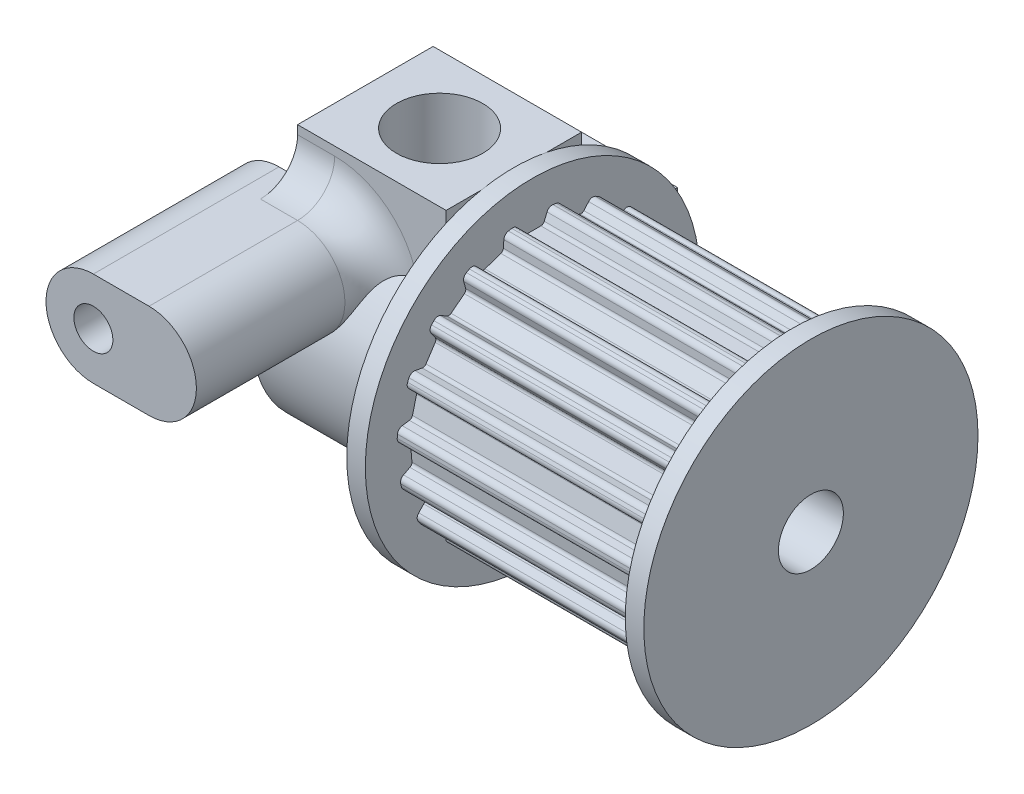
SolidWorks part; units mm, degrees
material "PLA Black"
ref_plane "Front" through (0, 0, 0) normal (0, 0, 1) x (1, 0, 0)
ref_plane "Top" through (0, 0, 0) normal (0, 1, 0) x (1, 0, 0)
ref_plane "Right" through (0, 0, 0) normal (1, 0, 0) x (0, 0, -1)
sketch "Sketch1" plane through (0, 0, 0) normal (1, 0, 0) x (0, 0, -1)
  line L0 (1.118, 1) -> (-1.118, 1) construction
  line L1 (-3.65, 4.8249) -> (3.65, 4.8249)
  line L2 (4.8249, 3.65) -> (4.8249, -3.65)
  line L3 (0, 0) -> (11.6334, 0) construction
  line L4 (0, 0) -> (0, 8.6732) construction
  arc A0 (-1.118, 1) -> (1.118, 1) centre (0, 0) ccw construction
  circle A1 centre (0, 0) radius 1.75
  arc A2 (4.8249, -3.65) -> (-3.65, 4.8249) centre (0, 0) cw
  arc A3 (4.8249, 3.65) -> (3.65, 4.8249) centre (0, 0) ccw
  dimension "D1" = 3
  dimension "D3" = 0.25
  dimension "D5" = 6.05
  dimension "D2" = 1
  dimension "D4" = 7.3
extrude "Boss-Extrude1" add sketch "Sketch1" along normal mid plane 8
sketch "Sketch2" plane through (0, 4.8249, 0) normal (0, 1, 0) x (1, 0, 0)
  circle A0 centre (0, 0) radius 2.325
  dimension "D1" = 4.65
extrude "Cut-Extrude1" cut sketch "Sketch2" against normal blind 5
sketch "Sketch7" plane through (4, 0, 0) normal (1, 0, 0) x (0, 0, -1)
  circle A0 centre (0, 0) radius 1.75 construction
  circle A1 centre (0, 0) radius 7.3
  circle A2 centre (0, 0) radius 1.75
  dimension "D1" = 14.6
extrude "Boss-Extrude5" add sketch "Sketch7" along normal blind 15
sketch "Sketch8" plane through (19, 0, 0) normal (1, 0, 0) x (0, 0, -1)
  line L0 (-0.4541, 6.5499) -> (0.4528, 6.5499)
  line L1 (0.6374, 6.6734) -> (0.7865, 7.0333)
  line L2 (-0.6389, 6.6734) -> (-0.788, 7.0333)
  line L6 (0, 9.2013) -> (0, 0) construction
  arc A0 (0.4528, 6.5499) -> (0.6374, 6.6734) centre (0.4526, 6.7499) ccw
  arc A1 (-0.4541, 6.5499) -> (-0.6389, 6.6734) centre (-0.4541, 6.7499) cw
  arc A2 (0.7865, 7.0333) -> (1.1093, 7.2152) centre (1.0638, 6.9187) cw
  arc A3 (-0.788, 7.0333) -> (-1.1108, 7.215) centre (-1.0652, 6.9185) ccw
  circle A4 centre (0, 0) radius 7.3 construction
  arc A5 (-1.1108, 7.215) -> (1.1093, 7.2152) centre (0, 0) cw
  point P3 (-0.0007, 6.5499)
  point P15 (0, 9.84)
extrude "Cut-Extrude3" cut sketch "Sketch8" against normal up to surface (15 mm away) up to face at (4, 0, -7.3)
pattern_circular "CirPattern1" count 19 over 360 about axis through (19, 0, 0) along (-1, 0, 0) of "Cut-Extrude3"
sketch "Sketch9" plane through (19, 0, 0) normal (1, 0, 0) x (0, 0, -1)
  circle A0 centre (0, 0) radius 9
  circle A1 centre (0, 0) radius 1.75 construction
  circle A2 centre (0, 0) radius 1.75
  dimension "D1" = 18
extrude "Boss-Extrude6" add sketch "Sketch9" along normal blind 1
sketch "Sketch10" plane through (4, 0, 0) normal (-1, 0, 0) x (0, 0, 1)
  circle A0 centre (0, 0) radius 9
  circle A1 centre (0, 0) radius 9 construction
  circle A2 centre (0, 0) radius 1.75 construction
  circle A3 centre (0, 0) radius 1.75
extrude "Boss-Extrude7" add sketch "Sketch10" against normal blind 1
sketch "Sketch3" plane through (0, 0, -4.8249) normal (0, 0, -1) x (-1, 0, 0)
  circle A0 centre (0, 0) radius 2.325
  dimension "D1" = 4.65
extrude "Cut-Extrude2" cut sketch "Sketch3" against normal blind 5
sketch "Sketch4" plane through (0, 4.8249, 0) normal (0, 1, 0) x (1, 0, 0)
  line L0 (4, 3.65) -> (-4, 3.65) construction
  line L2 (4, -3.65) -> (-4, -3.65) construction
  line L3 (-4, 3.65) -> (-4, -3.65) construction
  line L4 (4, 3.65) -> (-4, 3.65)
  line L5 (4, 3.65) -> (4, -3.65)
  line L6 (4, -3.65) -> (-4, -3.65)
  line L7 (-4, 3.65) -> (-4, -3.65)
  line L8 (4, 7.3) -> (4, -7.3) construction
  circle A0 centre (0, 0) radius 2.325 construction
  circle A1 centre (0, 0) radius 2.325
extrude "Boss-Extrude2" add sketch "Sketch4" along normal blind 4
sketch "Sketch5" plane through (0, 0, -4.8249) normal (0, 0, -1) x (-1, 0, 0)
  line L0 (-4, 3.65) -> (4, 3.65) construction
  line L1 (4, -3.65) -> (4, 3.65) construction
  line L2 (-4, -3.65) -> (4, -3.65) construction
  line L4 (-4, 3.65) -> (4, 3.65)
  line L5 (4, -3.65) -> (4, 3.65)
  line L6 (-4, -3.65) -> (4, -3.65)
  line L7 (-4, -3.65) -> (-4, 3.65)
  line L8 (-4, -7.3) -> (-4, 7.3) construction
  circle A0 centre (0, 0) radius 2.325 construction
  circle A1 centre (0, 0) radius 2.325
extrude "Boss-Extrude3" add sketch "Sketch5" along normal blind 4
ref_axis "Axis1" through (20, 0, 0) along (-1, 0, 0)
sketch "Sketch6" plane through (0, 0, 3.65) normal (0, 0, 1) x (1, 0, 0)
  line L0 (-4, 8.8249) -> (-4, 4.8249) construction
  line L2 (-2, 6.3555) -> (-5, 6.3555)
  line L3 (-5, 1.2545) -> (-2, 1.2545)
  line L6 (20, 0) -> (-4, 0) construction
  circle A0 centre (-5, 3.805) radius 1.0505
  arc A1 (-5, 6.3555) -> (-5, 1.2545) centre (-5, 3.805) ccw
  arc A2 (-2, 6.3555) -> (-2, 1.2545) centre (-2, 3.805) cw
  dimension "D1" = 2.101
  dimension "D2" = 3.805
  dimension "D3" = 1.5
  dimension "D4" = 1
  dimension "D5" = 3
extrude "Boss-Extrude4" add sketch "Sketch6" along normal blind 10
fillet "Fillet1" radius 2 2 edges at (-0.6029, 5.9388, 3.65) (-3, 6.3555, 3.65)
equation "\"knee_angle\"= 70"
equation "\"ankle_angle\" = 80"
equation "\"hip_angle\" = 40"
equation "\"spring_ankle_parallel_arm_diameter\"= 1.5"
equation "\"spring_ankle_parallel_arm_length\"= 13"
equation "\"spring_ankle_parallel_intern_diameter\"= 5.7"
equation "\"spring_ankle_parallel_angle\"= \"ankle_angle\""
equation "\"spring_ankle_parallel_turns\"= 3"
equation "\"spring_ankle_parallel_pitch\"= \"spring_ankle_parallel_arm_diameter\" * 1.01"
equation "\"spring_ankle_parallel_cutting_distance\"= (1-\"spring_ankle_parallel_angle\" / 360) * \"spring_ankle_parallel_pitch\""
equation "\"spring_ankle_serial_arm_diameter\"= 1.91"
equation "\"spring_ankle_serial_arm_length\"= 10"
equation "\"spring_ankle_serial_intern_diameter\"= 5.7"
equation "\"spring_ankle_serial_angle\"= \"90\""
equation "\"spring_ankle_serial_turns\"= 3"
equation "\"spring_ankle_serial_pitch\"= \"spring_ankle_serial_arm_diameter\" * 1.01"
equation "\"spring_ankle_serial_cutting_distance\"= (1-\"spring_ankle_serial_angle\" / 360) * \"spring_ankle_serial_pitch\""
equation "\"spring_knee_parallel_arm_diameter\"= 1.5"
equation "\"spring_knee_parallel_arm_length\"= 13"
equation "\"spring_knee_parallel_intern_diameter\"= 5.7"
equation "\"spring_knee_parallel_angle\"= -\"knee_angle\" + 90"
equation "\"spring_knee_parallel_turns\"= 3"
equation "\"spring_knee_parallel_pitch\"= \"spring_knee_parallel_arm_diameter\" * 1.01"
equation "\"spring_knee_parallel_cutting_distance\"= (1-(\"spring_knee_parallel_angle\") / 360) * \"spring_knee_parallel_pitch\""
equation "\"spring_knee_serial_arm_diameter\"= 1.91"
equation "\"spring_knee_serial_arm_length\"= 10"
equation "\"spring_knee_serial_intern_diameter\"= 5.7"
equation "\"spring_knee_serial_angle\"= \"90\""
equation "\"spring_knee_serial_turns\"= 3"
equation "\"spring_knee_serial_pitch\"= \"spring_knee_serial_arm_diameter\" * 1.01"
equation "\"spring_knee_serial_cutting_distance\"= (1-\"spring_knee_serial_angle\" / 360) * \"spring_knee_serial_pitch\""
equation "\"D2@Sketch6\" = ( \"spring_ankle_serial_intern_diameter\" + \"spring_ankle_serial_arm_diameter\" ) / 2"
equation "\"D1@Sketch6\" = \"spring_ankle_serial_arm_diameter\" * 1.1"
